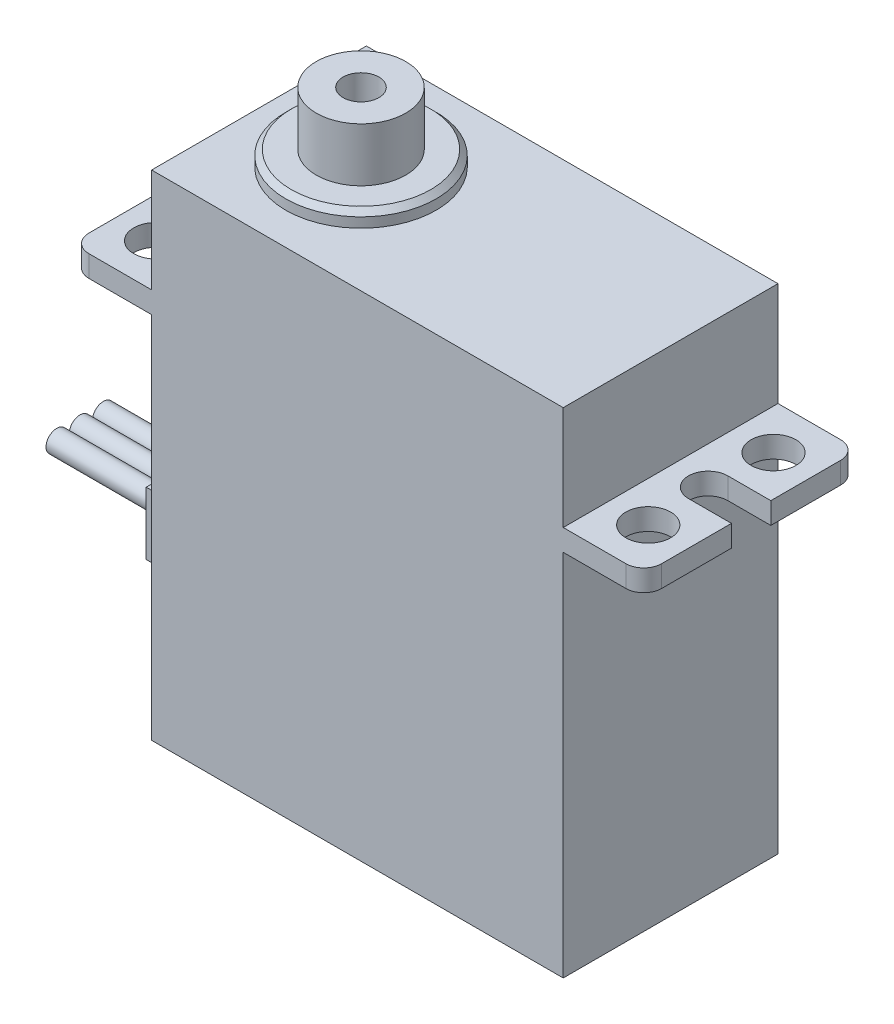
SolidWorks part; units mm, degrees
ref_plane "Front Plane" through (0, 0, 0) normal (0, 0, 1) x (1, 0, 0)
ref_plane "Top Plane" through (0, 0, 0) normal (0, 1, 0) x (1, 0, 0)
ref_plane "Right Plane" through (0, 0, 0) normal (1, 0, 0) x (0, 0, -1)
sketch "Эскиз1" plane through (0, 0, 0) normal (0, 0, 1) x (1, 0, 0)
  line L0 (0, 5.0732) -> (0, -2.902) construction
  line L1 (-11.5, -13.8) -> (11.5, -13.8)
  line L2 (-11.5, -13.8) -> (-11.5, 13.8)
  line L3 (-11.5, 13.8) -> (11.5, 13.8)
  line L4 (11.5, -13.8) -> (11.5, 13.8)
  line L5 (-11.5, -13.8) -> (11.5, 13.8) construction
  line L6 (-11.5, 13.8) -> (11.5, -13.8) construction
  line L7 (-16, 6.8) -> (-11.5, 6.8)
  line L8 (-16, 6.8) -> (-16, 8)
  line L9 (-16, 8) -> (-11.5, 8)
  line L10 (-11.5, 6.8) -> (-11.5, 8)
  line L11 (-16, 6.8) -> (-11.5, 8) construction
  line L12 (-16, 8) -> (-11.5, 6.8) construction
  line L13 (16, 8) -> (11.5, 8)
  line L14 (11.5, 6.8) -> (11.5, 8)
  line L15 (16, 6.8) -> (11.5, 6.8)
  line L16 (16, 6.8) -> (16, 8)
  point P0 (0, 0)
  point P5 (-13.75, 7.4)
  dimension "D1" = 23
  dimension "D2" = 27.6
  dimension "D3" = 20.6
  dimension "D4" = 1.2
  dimension "D5" = 32
extrude "Бобышка-Вытянуть1" add sketch "Эскиз1" along normal mid plane 12 contours L1 L4 L3 L2 | L9 L8 L7 L2 | L15 L16 L13 L4 region at (0, 0, 0) region at (-13.75, 7.4, 0) region at (13.75, 7.4, 0)
sketch "Эскиз2" plane through (0, 13.8, 0) normal (0, 1, 0) x (1, 0, 0)
  line L0 (-11.5, 0) -> (11.5, 0) construction
  line L1 (-11.5, -6) -> (-11.5, 6) construction
  line L2 (11.5, -6) -> (11.5, 6) construction
  line L3 (-11.5, -6) -> (-11.5, 6) construction
  circle A0 centre (-5.8, 0) radius 4.2
  dimension "D1" = 8.4
  dimension "D2" = 1.5
extrude "Бобышка-Вытянуть2" add sketch "Эскиз2" along normal blind 0.85
chamfer "Фаска1" distance 0.3 angle 45 1 edges at (-5.8, 14.65, 4.2)
sketch "Эскиз4" plane through (0, 14.65, 0) normal (0, 1, 0) x (1, 0, 0)
  circle A0 centre (-5.8, 0) radius 2.5
  circle A1 centre (-5.8, 0) radius 3.9
  circle A2 centre (-5.8, 0) radius 3.9 construction
  circle A3 centre (-5.8, 0) radius 1
  dimension "D2" = 5
  dimension "D3" = 2
  dimension "D1" = 0
extrude "Бобышка-Вытянуть3" add sketch "Эскиз4" along normal blind 3
sketch "Эскиз3" plane through (0, 8, 0) normal (0, 1, 0) x (1, 0, 0)
  line L0 (-13.75, 6) -> (-13.75, -6) construction
  line L1 (-16, 6) -> (-11.5, 6) construction
  line L2 (-16, -6) -> (-11.5, -6) construction
  line L3 (0, -6) -> (0, 6) construction
  line L4 (-11.5, -6) -> (11.5, -6) construction
  line L5 (-11.5, 6) -> (11.5, 6) construction
  line L6 (-16, 0) -> (16, 0) construction
  line L7 (-16, -6) -> (-16, 6) construction
  line L8 (16, -6) -> (16, 6) construction
  line L9 (-16, 1.1) -> (-13.6, 1.1)
  line L10 (-13.6, -1.1) -> (-16, -1.1)
  line L11 (-12.5, 4.2867) -> (-12.5, 2.4321) construction
  line L12 (-16, 1.1) -> (-16, -1.1)
  line L13 (16, 1.1) -> (13.6, 1.1)
  line L14 (13.6, -1.1) -> (16, -1.1)
  line L15 (16, 1.1) -> (16, -1.1)
  circle A0 centre (-13.75, 3.5) radius 1.25
  circle A1 centre (-13.75, -3.5) radius 1.25
  circle A2 centre (13.75, -3.5) radius 1.25
  circle A3 centre (13.75, 3.5) radius 1.25
  arc A4 (-13.6, 1.1) -> (-13.6, -1.1) centre (-13.6, 0) cw
  arc A5 (13.6, 1.1) -> (13.6, -1.1) centre (13.6, 0) ccw
  dimension "D1" = 2.5
  dimension "D2" = 7
  dimension "D3" = 12
  dimension "D4" = 2.5
  dimension "D5" = 2.2
  dimension "D6" = 1.1
extrude "Вырез-Вытянуть1" cut sketch "Эскиз3" against normal through all both and the other way through all
fillet "Скругление1" radius 1 4 edges at (-16, 7.4, -6) (16, 7.4, -6) (16, 7.4, 6) (-16, 7.4, 6)
sketch "Эскиз5" plane through (-11.5, 0, 0) normal (-1, 0, 0) x (0, 0, 1)
  line L0 (0, -13.8) -> (0, 0) construction
  line L1 (6, -13.8) -> (-6, -13.8) construction
  line L2 (-6, -6.65) -> (6, -6.65) construction
  line L3 (-6, -13.8) -> (-6, 6.8) construction
  line L4 (6, -13.8) -> (6, 6.8) construction
  line L6 (-2.8, -8.4) -> (2.8, -8.4)
  line L7 (-2.8, -8.4) -> (-2.8, -4.9)
  line L8 (-2.8, -4.9) -> (2.8, -4.9)
  line L9 (2.8, -8.4) -> (2.8, -4.9)
  line L10 (-2.8, -8.4) -> (2.8, -4.9) construction
  line L11 (-2.8, -4.9) -> (2.8, -8.4) construction
  point P11 (0, -6.65)
  dimension "D1" = 5.4
  dimension "D2" = 3.5
  dimension "D3" = 5.6
extrude "Бобышка-Вытянуть4" add sketch "Эскиз5" along normal blind 3.5
sketch "Эскиз6" plane through (-15, 0, 0) normal (-1, 0, 0) x (0, 0, 1)
  line L0 (-2.8, -6.65) -> (2.8, -6.65) construction
  line L1 (0, -4.9) -> (0, -8.4) construction
  line L4 (2.8, -8.4) -> (2.8, -4.9)
  line L5 (2.8, -4.9) -> (-2.8, -4.9)
  line L6 (-2.8, -4.9) -> (-2.8, -8.4)
  line L7 (-2.8, -8.4) -> (2.8, -8.4)
  line L8 (2.8, -8.4) -> (2.8, -4.9) construction
  line L9 (2.8, -4.9) -> (-2.8, -4.9) construction
  line L10 (-2.8, -4.9) -> (-2.8, -8.4) construction
  line L11 (-2.8, -8.4) -> (2.8, -8.4) construction
  circle A0 centre (0, -6.65) radius 0.6
  circle A1 centre (1.3, -6.65) radius 0.6
  circle A2 centre (-1.3, -6.65) radius 0.6
  dimension "D2" = 1.2
  dimension "D3" = 0.1
  dimension "D4" = 0.1
  dimension "D1" = 0
extrude "Бобышка-Вытянуть7" add sketch "Эскиз6" along normal blind 6.5
equation "\"D4@Эскиз3\"=\"D3@Эскиз3\"/2 - \"D2@Эскиз3\"/2"
equation "\"D6@Эскиз3\"=\"D5@Эскиз3\"/2"
